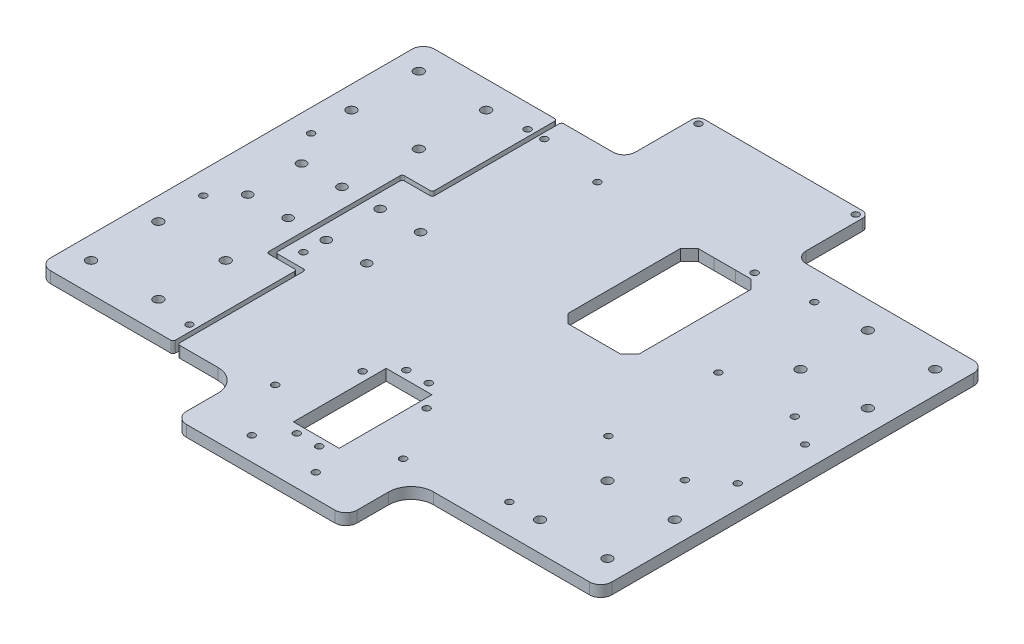
SolidWorks part; units mm, degrees
ref_plane "Front Plane" through (0, 0, 0) normal (0, 0, 1) x (1, 0, 0)
ref_plane "Top Plane" through (0, 0, 0) normal (0, 1, 0) x (1, 0, 0)
ref_plane "Right Plane" through (0, 0, 0) normal (1, 0, 0) x (0, 0, -1)
sketch "草图1" plane through (0, 0, 0) normal (0, 1, 0) x (1, 0, 0)
  line L1 (-125, 100) -> (125, 100)
  line L2 (-125, 100) -> (-125, -100)
  line L3 (-125, -100) -> (125, -100)
  line L4 (125, 100) -> (125, -100)
  line L5 (-125, 100) -> (125, -100) construction
  line L6 (-125, -100) -> (125, 100) construction
  point P0 (0, 0)
  dimension "D1" = 250
  dimension "D2" = 200
extrude "凸台-拉伸1" add sketch "草图1" along normal blind 5
sketch "草图2" plane through (0, 5, 0) normal (0, 1, 0) x (1, 0, 0)
  line L1 (-125, -100) -> (-63, -100)
  line L2 (-125, -100) -> (-125, -71)
  line L3 (-125, -71) -> (-63, -71)
  line L4 (-63, -100) -> (-63, -71)
  line L7 (65, -71) -> (125, -71)
  line L8 (65, -71) -> (65, -100)
  line L9 (65, -100) -> (125, -100)
  line L10 (125, -71) -> (125, -100)
  dimension "D1" = 62
  dimension "D2" = 60
extrude "切除-拉伸1" cut sketch "草图2" against normal through all
sketch "草图12" plane through (0, 5, 0) normal (0, 1, 0) x (1, 0, 0)
  circle A10 centre (85, -28) radius 2.1
  circle A11 centre (115, -28) radius 2.1
  circle A12 centre (115, -58) radius 2.1
  circle A13 centre (85, -58) radius 2.1
  circle A16 centre (-115, -28) radius 2.1
  circle A17 centre (-85, -28) radius 2.1
  circle A18 centre (-85, -58) radius 2.1
  circle A19 centre (-115, -58) radius 2.1
  circle A20 centre (-115, 88) radius 2.1
  circle A21 centre (-85, 88) radius 2.1
  circle A22 centre (-115, 58) radius 2.1
  circle A23 centre (-85, 58) radius 2.1
  circle A24 centre (115, 88) radius 2.1
  circle A25 centre (85, 88) radius 2.1
  circle A26 centre (115, 58) radius 2.1
  circle A27 centre (85, 58) radius 2.1
extrude "切除-拉伸11" cut sketch "草图12" against normal blind 10
sketch "草图15" plane through (0, 5, 0) normal (0, 1, 0) x (1, 0, 0)
  line L0 (125, 14.5) -> (62.1352, 14.5) construction
  line L1 (125, -71) -> (125, 100) construction
  circle A0 centre (-115, 40) radius 1.5
  circle A1 centre (-115, -8) radius 1.5
  circle A3 centre (115, 0) radius 1.5
  circle A4 centre (115, 30) radius 1.5
  circle A7 centre (-68.3539, -60.7936) radius 1.5
  circle A8 centre (-68.3539, 89.7936) radius 1.5
  circle A9 centre (62.1453, 87) radius 1.5
  circle A10 centre (71.3529, -58) radius 1.5
  dimension "D1" = 3
extrude "切除-拉伸14" cut sketch "草图15" against normal blind 15
sketch "草图16" plane through (0, 5, 0) normal (0, 1, 0) x (1, 0, 0)
  line L1 (65, -100) -> (40.5547, -100)
  line L2 (65, -100) -> (65, -71)
  line L3 (65, -71) -> (40.5547, -71)
  line L4 (40.5547, -100) -> (40.5547, -71)
  line L5 (-63, -100) -> (-35.5315, -100)
  line L6 (-63, -100) -> (-63, -71)
  line L7 (-63, -71) -> (-35.5315, -71)
  line L8 (-35.5315, -100) -> (-35.5315, -71)
extrude "切除-拉伸15" cut sketch "草图16" against normal blind 15
fillet "圆角1" radius 10 2 edges at (40.5547, 2.5, 71) (-35.5315, 2.5, 71)
sketch "草图20" plane through (0, 0, -100) normal (0, 0, -1) x (-1, 0, 0)
  line L0 (-125, 0) -> (125, 0) construction
  line L1 (-40.5547, 5) -> (35.5315, 5)
  line L2 (-40.5547, 5) -> (-40.5547, 0)
  line L3 (-40.5547, 0) -> (35.5315, 0)
  line L4 (35.5315, 5) -> (35.5315, 0)
  line L5 (-40.5547, 0) -> (-40.5547, 5) construction
  line L6 (35.5315, 5) -> (35.5315, 0) construction
extrude "凸台-拉伸3" add sketch "草图20" along normal blind 33
fillet "圆角3" radius 3 2 edges at (-35.5315, 2.5, -133) (40.5547, 2.5, -133)
fillet "圆角4" radius 5 8 edges at (-35.5315, 2.5, -100) (125, 2.5, 71) (125, 2.5, -100) (40.5547, 2.5, -100) (-125, 2.5, -100) (-125, 2.5, 71) (40.5547, 2.5, 100) (-35.5315, 2.5, 100)
sketch "草图24" plane through (0, 5, 0) normal (0, 1, 0) x (1, 0, 0)
  line L1 (-71.3326, 58) -> (80.0052, 58)
  line L2 (-71.3326, 58) -> (-71.3326, -15.8056)
  line L3 (-71.3326, -15.8056) -> (80.0052, -15.8056)
  line L4 (80.0052, 58) -> (80.0052, -15.8056)
sketch "草图25" plane through (0, 5, 0) normal (0, 1, 0) x (1, 0, 0)
  line L1 (-7.6588, -33.8864) -> (12.7236, -33.8864)
  line L2 (-7.6588, -33.8864) -> (-7.6588, -75.2024)
  line L3 (-7.6588, -75.2024) -> (12.7236, -75.2024)
  line L4 (12.7236, -33.8864) -> (12.7236, -75.2024)
extrude "切除-拉伸19" cut sketch "草图25" against normal blind 10
sketch "草图26" plane through (0, 5, 0) normal (0, 1, 0) x (1, 0, 0)
  circle A0 centre (2.5116, -65) radius 28.5 construction
  circle A1 centre (-25.9884, -65) radius 1.5
  circle A2 centre (-11.7384, -40.3183) radius 1.5
  circle A3 centre (16.7616, -40.3183) radius 1.5
  circle A4 centre (31.0116, -65) radius 1.5
  circle A5 centre (16.7616, -89.6817) radius 1.5
  circle A6 centre (-11.7384, -89.6817) radius 1.5
  circle A7 centre (-2.4884, -30.1) radius 1.5
  circle A8 centre (7.5116, -30.1) radius 1.5
  circle A9 centre (-2.4884, -78.9) radius 1.5
  circle A10 centre (7.5116, -78.9) radius 1.5
  point P18 (2.5116, -65)
  dimension "D1" = 6
extrude "切除-拉伸20" cut sketch "草图26" against normal blind 10
sketch "草图28" plane through (0, 5, 0) normal (0, 1, 0) x (1, 0, 0)
  line L1 (-63.4541, 100) -> (-63.4541, 42.4653)
  line L2 (-40.5315, 100) -> (-120, 100) construction
  line L3 (-63.4541, 42.4653) -> (-76.8555, 42.4653)
  line L4 (-76.8555, 42.4653) -> (-76.8555, 26.2661)
  line L5 (-65.4541, 100) -> (-65.4541, 44.4653)
  line L6 (-65.4541, 44.4653) -> (-78.8555, 44.4653)
  line L7 (-78.8555, 44.4653) -> (-78.8555, 26.2661)
  line L9 (-85.2118, 14.2661) -> (-52.168, 14.2661) construction
  line L10 (-78.8555, 26.2661) -> (-78.8555, 2.2661)
  line L11 (-76.8555, 26.2661) -> (-76.8555, 2.2661)
  line L12 (-78.8555, -15.9331) -> (-78.8555, 2.2661)
  line L13 (-65.4541, -15.9331) -> (-78.8555, -15.9331)
  line L14 (-65.4541, -71) -> (-65.4541, -15.9331)
  line L15 (-76.8555, -13.9331) -> (-76.8555, 2.2661)
  line L16 (-63.4541, -13.9331) -> (-76.8555, -13.9331)
  line L17 (-63.4541, -71) -> (-63.4541, -13.9331)
  line L18 (-65.4541, 100) -> (-63.4541, 100)
  line L19 (-65.4541, -71) -> (-63.4541, -71)
  line L20 (-45.5315, -71) -> (-120, -71) construction
  point P21 (-76.8555, 14.2661)
  point P22 (-78.8555, 14.2661)
  dimension "D1" = 2
extrude "切除-拉伸22" cut sketch "草图28" against normal blind 10
sketch "草图27" plane through (0, 5, 0) normal (0, 1, 0) x (1, 0, 0)
  line L0 (-78.8555, 36.5905) -> (-76.8555, 36.5905) construction
  line L1 (-76.4993, -2.7339) -> (-76.4993, -74.1543) construction
  line L2 (-78.8555, 44.4653) -> (-78.8555, -15.9331) construction
  line L3 (-65.4541, 100) -> (-120, 100) construction
  line L4 (-76.8555, -13.9331) -> (-76.8555, 42.4653) construction
  line L5 (-81.4993, 31.2661) -> (-76.4993, 31.2661) construction
  line L6 (-77.8555, 36.5905) -> (-77.8555, 27.4867) construction
  line L7 (-70.4993, 26.2661) -> (-70.4993, 25.8905) construction
  line L8 (-85.2118, 26.2661) -> (-85.2118, 25.8905) construction
  line L9 (-85.2118, 14.4789) -> (-60.044, 14.4789) construction
  line L10 (-106.5578, 14.4611) -> (-106.5578, 14.4968)
  line L11 (-106.5578, 14.4968) -> (-106.5578, 14.4611)
  line L15 (-81.4993, -2.3082) -> (-76.4993, -2.3082) construction
  line L16 (-60.044, 100) -> (-60.044, -71) construction
  line L18 (-60.044, 14.5) -> (-106.5578, 14.4611) construction
  line L20 (-85.2118, 24.2661) -> (-85.2118, 3.0674) construction
  circle A12 centre (-70.4993, 2.2661) radius 2
  circle A13 centre (-70.4993, 26.2661) radius 2
  circle A14 centre (-52.4993, 2.2661) radius 2
  circle A15 centre (-52.4993, 26.2661) radius 2
  circle A16 centre (-105.4993, 2.2661) radius 2
  circle A17 centre (-87.4993, 2.2661) radius 2
  circle A18 centre (-105.4993, 26.2661) radius 2
  circle A19 centre (-87.4993, 26.2661) radius 2
  point P42 (-106.5578, 14.4789)
extrude "切除-拉伸21" cut sketch "草图27" against normal blind 10 contours A16 | A12 | A14 | A15 | A13 | A18 | A19 | A17 region at (-70.4993, 5, -2.2661) region at (-70.4993, 5, -26.2661) region at (-52.4993, 5, -2.2661) region at (-52.4993, 5, -26.2661) region at (-105.4993, 5, -2.2661) region at (-87.4993, 5, -2.2661) region at (-105.4993, 5, -26.2661) region at (-87.4993, 5, -26.2661)
fillet "圆角5" radius 1 6 edges at (-65.4541, 2.5, 71) (-78.8555, 2.5, 15.9331) (-78.8555, 2.5, -44.4653) (-65.4541, 2.5, -44.4653) (-65.4541, 2.5, -100) (-65.4541, 2.5, 15.9331)
fillet "圆角6" radius 1 6 edges at (-63.4541, 2.5, -100) (-63.4541, 2.5, -42.4653) (-76.8555, 2.5, -42.4653) (-76.8555, 2.5, 13.9331) (-63.4541, 2.5, 13.9331) (-63.4541, 2.5, 71)
sketch "草图29" plane through (0, 5, 0) normal (0, 1, 0) x (1, 0, 0)
  circle A0 centre (-60.8647, 89.7936) radius 1.5
  dimension "D1" = 3
extrude "切除-拉伸23" cut sketch "草图29" against normal blind 10
sketch "草图30" plane through (0, 5, 0) normal (0, 1, 0) x (1, 0, 0)
  circle A0 centre (-70.8742, -7.5343) radius 1.5
extrude "切除-拉伸24" cut sketch "草图30" against normal blind 10
sketch "草图32" plane through (0, 5, 0) normal (0, 1, 0) x (1, 0, 0)
  circle A0 centre (67.9641, 38.5) radius 1.5
  circle A1 centre (67.9641, -10.5) radius 1.5
  circle A2 centre (101.9641, -10.5) radius 1.5
  circle A3 centre (101.9641, 38.5) radius 1.5
extrude "切除-拉伸27" cut sketch "草图32" against normal up to surface (5 mm away) contours A0 | A1 | A3 | A2 region at (67.9641, 5, -38.5) region at (67.9641, 5, 10.5) up to face at (-70.8742, 0, 9.0343)
sketch "草图36" plane through (0, 5, 0) normal (0, 1, 0) x (1, 0, 0)
  line L14 (15.653, 81.8069) -> (11.653, 77.807)
  line L15 (11.653, 77.807) -> (11.653, 54.7359)
  line L48 (11.653, 54.7359) -> (11.653, 27.8069)
  line L49 (11.653, 27.8069) -> (15.653, 23.8069)
  line L50 (15.653, 23.8069) -> (22.653, 23.8069)
  line L51 (22.653, 23.8069) -> (32.153, 23.8069)
  line L52 (32.153, 23.8069) -> (39.153, 23.8069)
  line L53 (39.153, 23.8069) -> (43.153, 27.8069)
  line L54 (43.153, 27.8069) -> (43.153, 54.7359)
  line L55 (43.153, 54.7359) -> (43.153, 77.8069)
  line L56 (43.153, 77.8069) -> (39.153, 81.8069)
  line L57 (39.153, 81.8069) -> (32.153, 81.8069)
  line L58 (32.153, 81.8069) -> (22.653, 81.8069)
  line L59 (22.653, 81.8069) -> (15.653, 81.8069)
  line L60 (15.653, 81.8069) -> (11.653, 77.807)
  line L61 (11.653, 77.807) -> (11.653, 54.7359)
  line L62 (11.653, 54.7359) -> (11.653, 27.8069)
  line L63 (11.653, 27.8069) -> (15.653, 23.8069)
  line L64 (15.653, 23.8069) -> (22.653, 23.8069)
  line L65 (22.653, 23.8069) -> (32.153, 23.8069)
  line L66 (32.153, 23.8069) -> (39.153, 23.8069)
  line L67 (39.153, 23.8069) -> (43.153, 27.8069)
  line L68 (43.153, 27.8069) -> (43.153, 54.7359)
  line L69 (43.153, 54.7359) -> (43.153, 77.8069)
  line L70 (43.153, 77.8069) -> (39.153, 81.8069)
  line L71 (39.153, 81.8069) -> (32.153, 81.8069)
  line L72 (32.153, 81.8069) -> (22.653, 81.8069)
  line L73 (22.653, 81.8069) -> (15.653, 81.8069)
  dimension "D2" = 0
extrude "切除-拉伸30" cut sketch "草图36" against normal blind 5
sketch "草图39" plane through (0, 0, 0) normal (0, -1, 0) x (1, 0, 0)
  line L0 (40.5547, -130) -> (40.5547, -105) construction
  line L1 (-32.4453, -85) -> (37.5547, -85) construction
  line L2 (-32.4453, -85) -> (-32.4453, -130) construction
  line L3 (-32.4453, -130) -> (37.5547, -130) construction
  line L4 (37.5547, -85) -> (37.5547, -130) construction
  line L5 (37.5547, -133) -> (-32.5315, -133) construction
  line L6 (-35.5315, -130) -> (-35.5315, -105) construction
  circle A0 centre (-32.4453, -130) radius 1.5
  circle A1 centre (-32.4453, -85) radius 1.5
  circle A2 centre (37.5547, -130) radius 1.5
  circle A3 centre (37.5547, -85) radius 1.5
  dimension "D6" = 3
  dimension "D1" = 3
  dimension "D2" = 70
  dimension "D3" = 45
  dimension "D4" = 3
  dimension "D5" = 3.0862
extrude "切除-拉伸31" cut sketch "草图39" against normal blind 5
